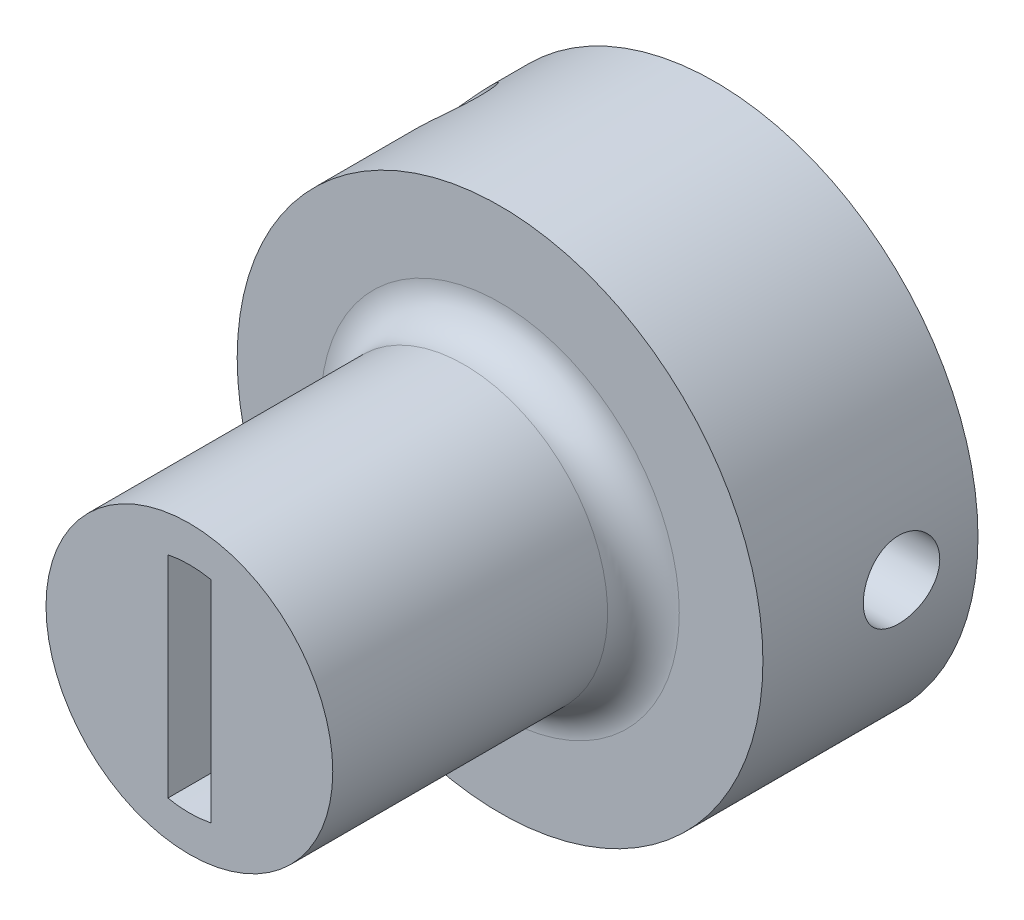
SolidWorks part; units mm, degrees
ref_plane "Front Plane" through (0, 0, 0) normal (0, 0, 1) x (1, 0, 0)
ref_plane "Top Plane" through (0, 0, 0) normal (0, 1, 0) x (1, 0, 0)
ref_plane "Right Plane" through (0, 0, 0) normal (1, 0, 0) x (0, 0, -1)
sketch "Sketch1" plane through (0, 0, 0) normal (0, 0, 1) x (1, 0, 0)
  circle A0 centre (0, 0) radius 2
  circle A1 centre (0, 0) radius 6
  dimension "D1" = 4
  dimension "D2" = 12
extrude "Boss-Extrude1" add sketch "Sketch1" along normal blind 9
sketch "Sketch2" plane through (0, 0, 9) normal (0, 0, 1) x (1, 0, 0)
  circle A1 centre (0, 0) radius 6
  circle A2 centre (0, 0) radius 6
  dimension "D1" = 0
extrude "Boss-Extrude2" add sketch "Sketch2" along normal blind 3
sketch "Sketch3" plane through (0, 0, 12) normal (0, 0, 1) x (1, 0, 0)
  line L0 (0, 0) -> (0, 6.2414) construction
  line L2 (0.9, 4.4091) -> (0.9, -4.4091)
  line L4 (-0.9, 4.4091) -> (-0.9, -4.4091)
  arc A0 (-0.9, 4.4091) -> (-0.9, -4.4091) centre (0, 0) ccw
  arc A1 (0.9, -4.4091) -> (0.9, 4.4091) centre (0, 0) ccw
  dimension "D2" = 9
  dimension "D4" = 0.9
extrude "Boss-Extrude3" add sketch "Sketch3" along normal blind 10
sketch "Sketch4" plane through (0, 0, 12) normal (0, 0, 1) x (1, 0, 0)
  circle A0 centre (0, 0) radius 6 construction
  circle A1 centre (0, 0) radius 6
  circle A2 centre (0, 0) radius 4.5
  dimension "D1" = 9
extrude "Boss-Extrude4" add sketch "Sketch4" along normal blind 10
sketch "Sketch5" plane through (0, 0, 9) normal (0, 0, -1) x (-1, 0, 0)
  circle A0 centre (0, 0) radius 11
  circle A1 centre (0, 0) radius 6 construction
  circle A2 centre (0, 0) radius 6
  dimension "D1" = 22
extrude "Boss-Extrude5" add sketch "Sketch5" along normal up to surface (9 mm away) up to face at (6, 0, 0)
sketch "Sketch6" plane through (0, 0, 0) normal (0, 0, -1) x (-1, 0, 0)
  line L0 (-11, 0) -> (11, 0) construction
  line L1 (0, -11) -> (0, 11) construction
  line L2 (0, 0) -> (7.851, 7.7046) construction
  line L7 (-6.7, 2.75) -> (-4, 2.75)
  line L8 (-6.7, 2.75) -> (-6.7, -2.75)
  line L9 (-6.7, -2.75) -> (-4, -2.75)
  line L10 (-4, 2.75) -> (-4, -2.75)
  line L11 (2.8558, 6.6556) -> (6.7081, 2.7301)
  line L12 (6.7081, 2.7301) -> (4.7811, 0.8389)
  line L13 (4.7811, 0.8389) -> (0.9288, 4.7644)
  line L14 (0.9288, 4.7644) -> (2.8558, 6.6556)
  circle A0 centre (0, 0) radius 11 construction
  dimension "D1" = 5.5
  dimension "D2" = 2.7
  dimension "D3" = 2.75
  dimension "D4" = 5.5
  dimension "D5" = 2.7
  dimension "D6" = 2.75
  dimension "D7" = 4
  dimension "D8" = 4
  dimension "D9" = 2.7
  dimension "D10" = 4.3
extrude "Cut-Extrude1" cut sketch "Sketch6" against normal blind 6.2
sketch "Sketch7" plane through (4, 0, 0) normal (1, 0, 0) x (0, 0, -1)
  line L4 (0, -2.75) -> (0, 2.75)
  line L5 (0, 2.75) -> (-6.2, 2.75)
  line L6 (-6.2, 2.75) -> (-6.2, -2.75)
  line L7 (-6.2, -2.75) -> (0, -2.75)
  line L10 (-6.2, 2.75) -> (-6.2, -2.75) construction
  circle A0 centre (-3.2, 0) radius 1.6
  dimension "D2" = 3.2
  dimension "D3" = 3
  dimension "D1" = 0
extrude "Cut-Extrude2" cut sketch "Sketch7" along normal through all
sketch "Sketch8" plane through (-2.8549, 2.8017, 0) normal (-0.7137, 0.7004, 0) x (0, 0, 1)
  line L4 (0, 2.75) -> (0, -2.75)
  line L5 (0, -2.75) -> (6.2, -2.75)
  line L6 (6.2, -2.75) -> (6.2, 2.75)
  line L7 (6.2, 2.75) -> (0, 2.75)
  line L10 (6.2, -2.75) -> (6.2, 2.75) construction
  circle A0 centre (3.2, 0) radius 1.6
  dimension "D2" = 3.2
  dimension "D3" = 3
  dimension "D1" = 0
extrude "Cut-Extrude3" cut sketch "Sketch8" along normal through all
fillet "Fillet1" radius 0.9 4 edges at (0.9, 0, 12) (-0.9, 0, 12) (0, -4.5, 12) (0, 4.5, 12)
fillet "Fillet2" radius 1.5 1 edges at (-6, 0, 9)
